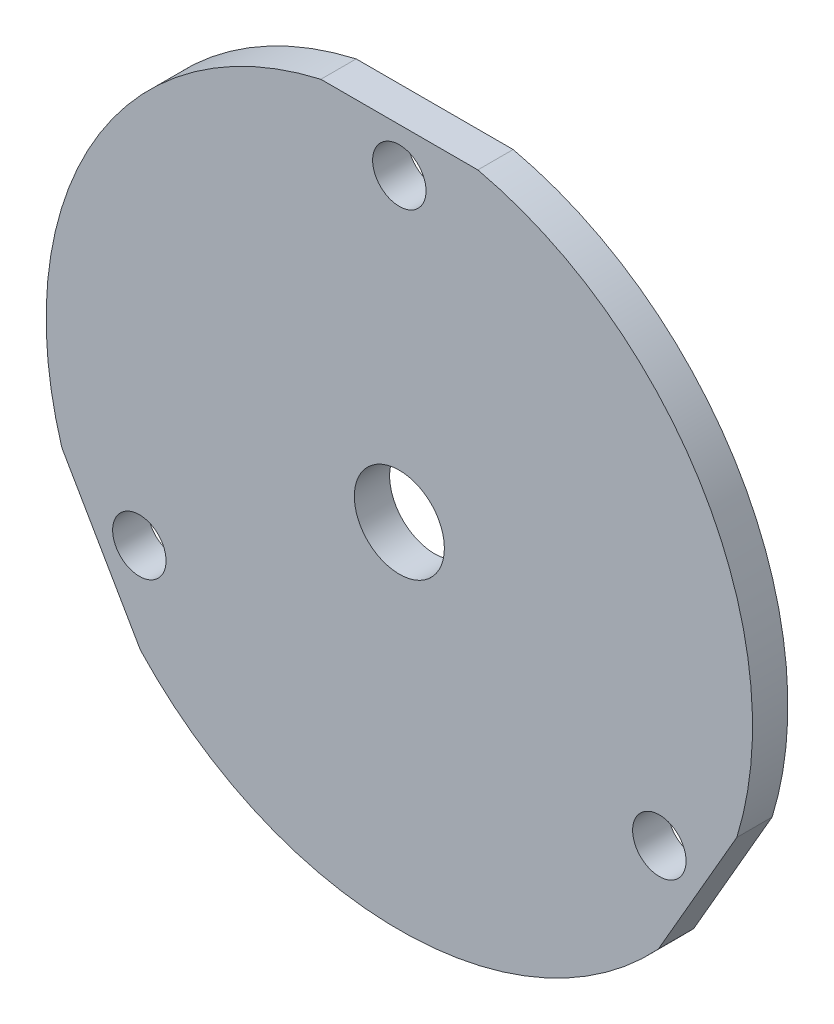
SolidWorks part; units mm, degrees
ref_plane "Front Plane" through (0, 0, 0) normal (0, 0, 1) x (1, 0, 0)
ref_plane "Top Plane" through (0, 0, 0) normal (0, 1, 0) x (1, 0, 0)
ref_plane "Right Plane" through (0, 0, 0) normal (1, 0, 0) x (0, 0, -1)
sketch "Sketch1" plane through (0, 0, 0) normal (0, 0, 1) x (1, 0, 0)
  circle A0 centre (0, 0) radius 40
  dimension "D1" = 80
extrude "Boss-Extrude1" add sketch "Sketch1" along normal blind 4 from offset 0.5
sketch "Sketch2" plane through (0, 0, 4.5) normal (0, 0, 1) x (1, 0, 0)
  line L0 (-8.8882, 39) -> (8.8882, 39)
  line L1 (38.2191, -11.8026) -> (29.3309, -27.1974)
  line L2 (-29.3309, -27.1974) -> (-38.2191, -11.8026)
  circle A0 centre (0, 34) radius 3.025
  circle A1 centre (0, 0) radius 40 construction
  arc A2 (8.8882, 39) -> (-8.8882, 39) centre (0, 0) ccw
  circle A3 centre (29.4449, -17) radius 3.025
  arc A4 (29.3309, -27.1974) -> (38.2191, -11.8026) centre (0, 0) ccw
  circle A5 centre (-29.4449, -17) radius 3.025
  arc A6 (-38.2191, -11.8026) -> (-29.3309, -27.1974) centre (0, 0) ccw
  point P2 (0, 0)
  point P19 (0, 0)
  dimension "D1" = 6.05
  dimension "D2" = 34
  dimension "D3" = 5
  dimension "D4" = 3
extrude "Cut-Extrude1" cut sketch "Sketch2" against normal blind 6
ref_axis "Axis1" through (0, 0, 4.5) along (0, 0, -1)
sketch "Sketch3" plane through (0, 0, 4.5) normal (0, 0, 1) x (1, 0, 0)
  circle A0 centre (0, 0) radius 5.1
  dimension "D1" = 10.2
extrude "Cut-Extrude2" cut sketch "Sketch3" against normal blind 15
